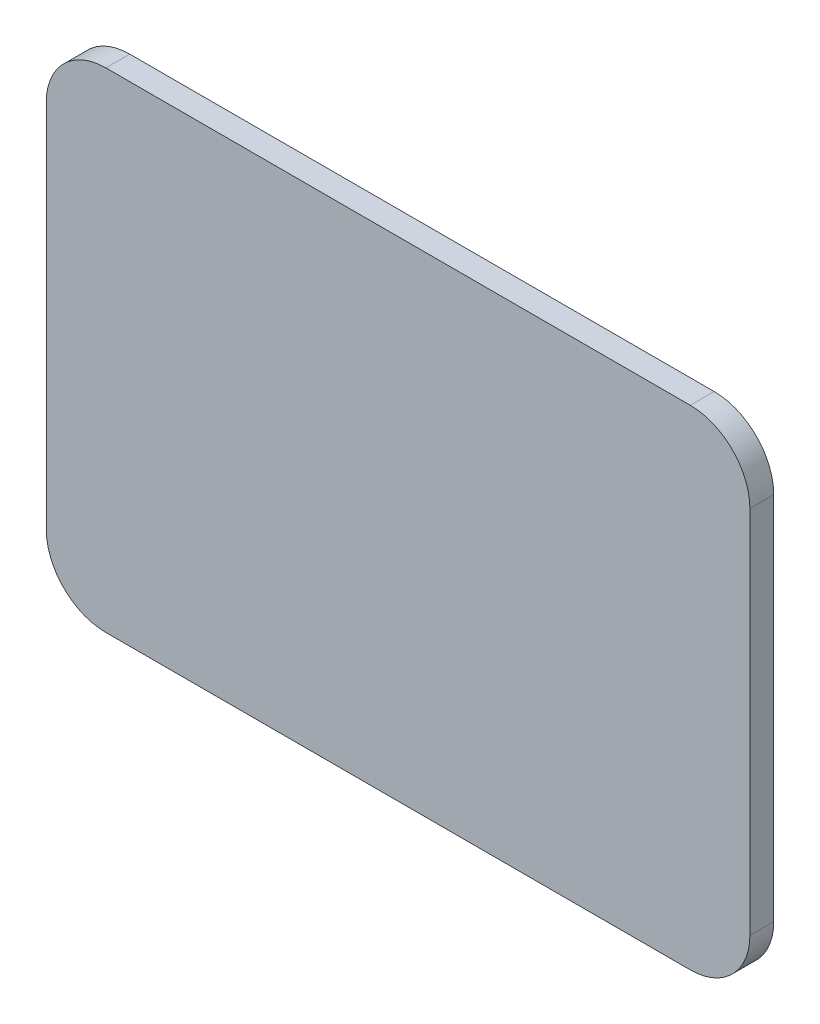
SolidWorks part; units mm, degrees
material "Custom Plastic"
ref_plane "X-Y Datum" through (0, 0, 0) normal (0, 0, 1) x (1, 0, 0)
ref_plane "X-Z Datum" through (0, 0, 0) normal (0, 1, 0) x (1, 0, 0)
ref_plane "Y-Z Datum" through (0, 0, 0) normal (1, 0, 0) x (0, 0, -1)
sketch "Sketch2" plane through (0, 0, 0) normal (0, 0, 1) x (1, 0, 0)
  line L4 (59, -31) -> (59, 31)
  line L5 (49, 41) -> (-49, 41)
  line L6 (-59, 31) -> (-59, -31)
  line L7 (-49, -41) -> (49, -41)
  line L8 (59, -31) -> (59, 31)
  line L9 (49, 41) -> (-49, 41)
  line L10 (-59, 31) -> (-59, -31)
  line L11 (-49, -41) -> (49, -41)
  arc A4 (59, 31) -> (49, 41) centre (49, 31) ccw
  arc A5 (-49, 41) -> (-59, 31) centre (-49, 31) ccw
  arc A6 (-59, -31) -> (-49, -41) centre (-49, -31) ccw
  arc A7 (49, -41) -> (59, -31) centre (49, -31) ccw
  arc A8 (59, 31) -> (49, 41) centre (49, 31) ccw
  arc A9 (-49, 41) -> (-59, 31) centre (-49, 31) ccw
  arc A10 (-59, -31) -> (-49, -41) centre (-49, -31) ccw
  arc A11 (49, -41) -> (59, -31) centre (49, -31) ccw
  dimension "D1" = 0
extrude "Boss-Extrude1" add sketch "Sketch2" along normal blind 4
